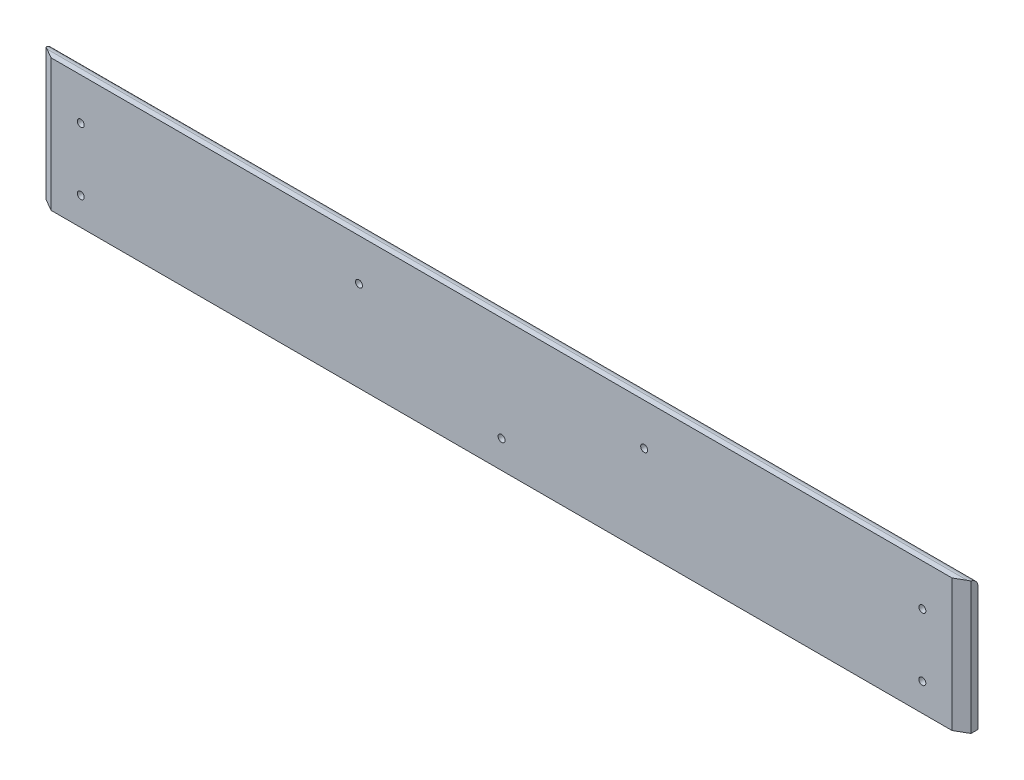
SolidWorks part; units mm, degrees
material "Настроенная пользователем пластмасса"
ref_plane "Спереди" through (0, 0, 0) normal (0, 0, 1) x (1, 0, 0)
ref_plane "Сверху" through (0, 0, 0) normal (0, 1, 0) x (1, 0, 0)
ref_plane "Справа" through (0, 0, 0) normal (1, 0, 0) x (0, 0, -1)
sketch "Эскиз1" plane through (0, 0, 0) normal (0, 0, 1) x (1, 0, 0)
  line L1 (-332.5, -47.5) -> (332.5, -47.5)
  line L2 (-332.5, -47.5) -> (-332.5, 47.5)
  line L3 (-332.5, 47.5) -> (332.5, 47.5)
  line L4 (332.5, -47.5) -> (332.5, 47.5)
  line L5 (0, 47.5) -> (0, -47.5) construction
  line L6 (-332.5, 0) -> (332.5, 0) construction
  point P0 (0, 0)
  dimension "D1" = 665
  dimension "D2" = 95
extrude "Бобышка-Вытянуть1" add sketch "Эскиз1" along normal mid plane 10
fillet "Скругление1" radius 6 1 edges at (0, 47.5, -5)
chamfer "Фаска1" distance 5 angle 60 2 edges at (332.5, 0, 5) (-332.5, 0, 5) first distance on face at (332.5, 8.5485, -0.0485) first distance on face at (-332.5, 8.5485, -0.0485)
sketch "Эскиз3" plane through (0, 0, 5) normal (0, 0, 1) x (1, 0, 0)
  line L0 (-323.8397, -47.5) -> (323.8397, -47.5) construction
  line L1 (-332.5, -47.5) -> (-332.5, 47.4161) construction
  line L2 (332.5, 47.4161) -> (332.5, -47.5) construction
  line L3 (0, -50) -> (0, 50) construction
  circle A0 centre (-302.5, -27.5) radius 2.5
  circle A1 centre (0, -27.5) radius 2.5
  circle A2 centre (302.5, -27.5) radius 2.5
  circle A3 centre (-302.5, 17.5) radius 2.5
  circle A4 centre (302.5, 17.5) radius 2.5
  circle A5 centre (-102.5, 17.5) radius 2.5
  circle A6 centre (102.5, 17.5) radius 2.5
  point P6 (0, 0)
  point P7 (0, 0)
  point P8 (0, 0)
  point P15 (0, 0)
  point P22 (0, 0)
  point P23 (-302.5, 20)
  point P24 (-200.6617, 5.8032)
  point P25 (53.7835, 13.3136)
  point P26 (0, 0)
  point P31 (0, 0)
  point P32 (0, 0)
  dimension "D1" = 5
  dimension "D2" = 20
  dimension "D3" = 30
  dimension "D4" = 30
  dimension "D5" = 45
  dimension "D6" = 200
  dimension "D7" = 200
extrude "Вырез-Вытянуть1" cut sketch "Эскиз3" against normal through all
chamfer "Фаска2" distance 2 angle 45 7 edges at (-300, -27.5, -5) (-300, 17.5, -5) (-100, 17.5, -5) (2.5, -27.5, -5) (105, 17.5, -5) (305, -27.5, -5) (305, 17.5, -5)
